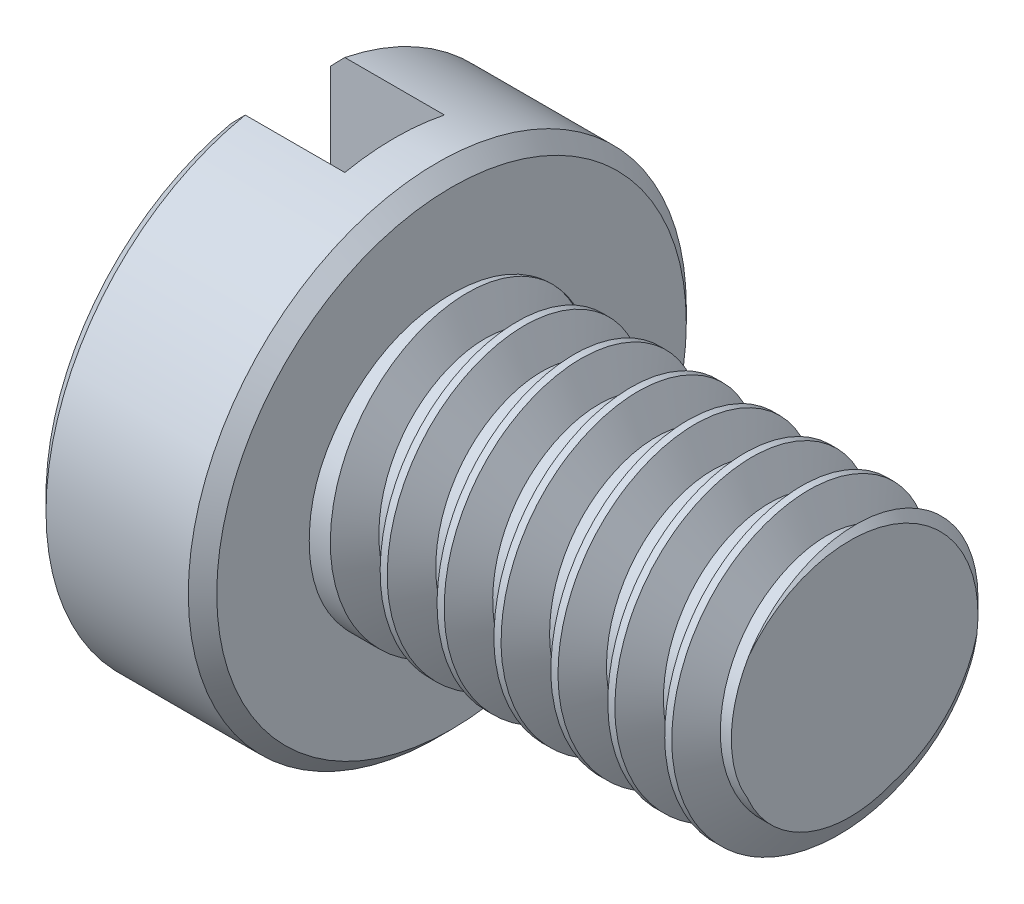
SolidWorks part; units mm, degrees
material "Латунь"
ref_plane "Front Plane" through (0, 0, 0) normal (0, 0, 1) x (1, 0, 0)
ref_plane "Top Plane" through (0, 0, 0) normal (0, 1, 0) x (1, 0, 0)
ref_plane "Right Plane" through (0, 0, 0) normal (1, 0, 0) x (0, 0, -1)
sketch "Эскиз1" plane through (0, 0, 0) normal (0, 0, 1) x (1, 0, 0)
  line L0 (0, 0) -> (4.8145, 0) construction
  line L1 (0, 0) -> (0, -1.75)
  line L2 (0, -1.75) -> (1.2, -1.75)
  line L3 (1.2, -1.75) -> (1.2, -1)
  line L4 (1.2, -1) -> (4, -1)
  line L5 (4, -1) -> (4, 0)
  line L6 (4, 0) -> (0, 0)
  dimension "D1" = 3.5
  dimension "D2" = 4
  dimension "D3" = 1.2
  dimension "D4" = 1
revolve "Повернуть1" add sketch "Эскиз1" angle 360 about L0
chamfer "Фаска1" distance 0.1 angle 45 3 edges at (4, 0, 1) (1.2, 0, 1.75) (0, 0, 1.75)
sketch "Эскиз2" plane through (0, 0, 0) normal (-1, 0, 0) x (0, 0, 1)
  line L1 (-0.35, 1.75) -> (0.35, 1.75)
  line L2 (-0.35, 1.75) -> (-0.35, -1.75)
  line L3 (-0.35, -1.75) -> (0.35, -1.75)
  line L4 (0.35, 1.75) -> (0.35, -1.75)
  line L5 (-0.35, 1.75) -> (0.35, -1.75) construction
  line L6 (-0.35, -1.75) -> (0.35, 1.75) construction
  circle A0 centre (0, 0) radius 1.75 construction
  point P0 (0, 0)
  dimension "D1" = 0.7
extrude "Вырез-Вытянуть1" cut sketch "Эскиз2" against normal blind 0.8
thread "Резьба1" pitch 0.4 method cut profile "Профиль резьбы1" start angle 0, offset 1, length 3.4, pitch 0.4, diameter 2
ref_plane "Плоскость1" through (4.9, 0, 1) normal (0, -1, 0) x (0, 0, 1)
sketch "Профиль резьбы1" plane through (4.9, 0, 1) normal (0, -1, 0) x (0, 0, 1)
  line L0 (0, 0) -> (0, 0.4) construction
  line L11 (0, 0) -> (0, 0.35)
  line L12 (0, 0.35) -> (-0.2165, 0.225)
  line L13 (-0.2165, 0.225) -> (-0.2165, 0.125)
  line L15 (-0.2165, 0.125) -> (0, 0)
  line L17 (-0.2165, 0.175) -> (0, 0.175) construction
  point P2 (0, 0)
  dimension "Pitch" = 0.4
  dimension "Profile_Angle" = 60
  dimension "Profile_Land" = 0.1
  dimension "Profile_Height" = 0.2165
